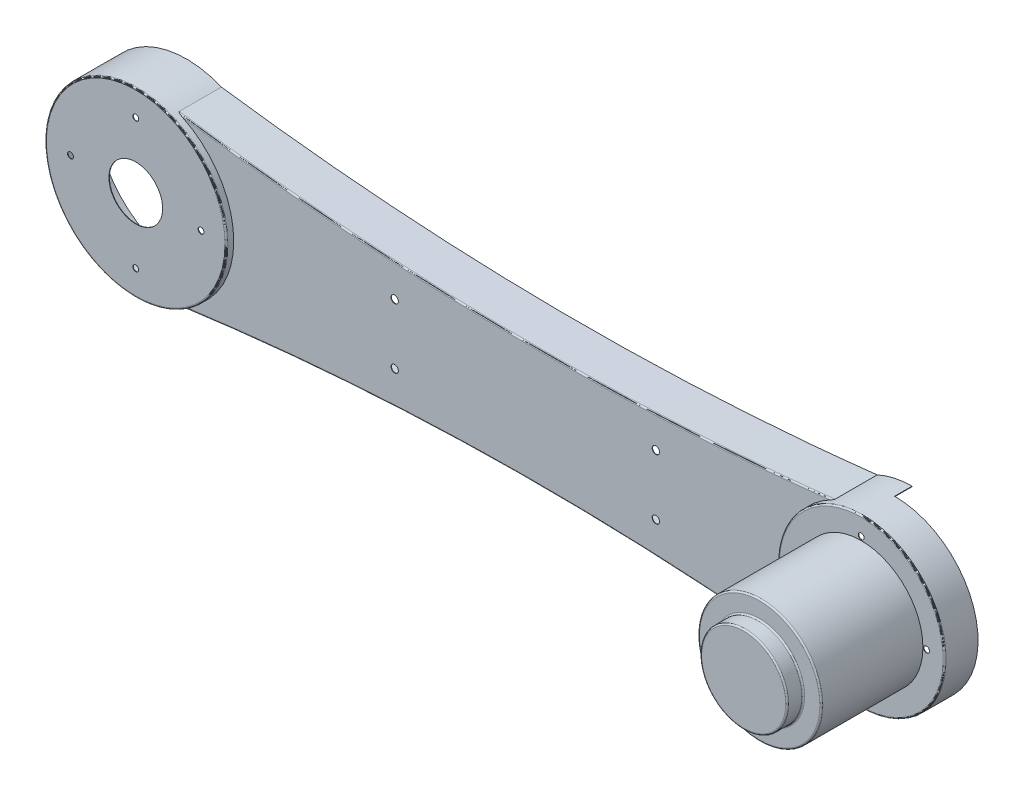
SolidWorks part; units mm, degrees
ref_plane "Front Plane" through (0, 0, 0) normal (0, 0, 1) x (1, 0, 0)
ref_plane "Top Plane" through (0, 0, 0) normal (0, 1, 0) x (1, 0, 0)
ref_plane "Right Plane" through (0, 0, 0) normal (1, 0, 0) x (0, 0, -1)
sketch "Sketch1" plane through (0, 0, 0) normal (0, 0, 1) x (1, 0, 0)
  line L0 (0, 0) -> (500, 0) construction
  line L1 (250, 0) -> (250, 152.9832) construction
  line L2 (24, 57.7083) -> (24, -57.7083) construction
  line L3 (476, 52.2518) -> (476, -52.2518) construction
  line L4 (0, 0) -> (0, 78.9019) construction
  circle A0 centre (0, 0) radius 62.5
  circle A1 centre (500, 0) radius 57.5
  spline S0 degree 2 poles (24, 57.7083) (249.6559, 26.362) (476, 52.2518) knots 0 0 0 1 1 1
  spline S1 degree 2 poles (24, -57.7083) (249.6559, -26.362) (476, -52.2518) knots 0 0 0 1 1 1
  dimension "D1" = 125
  dimension "D3" = 115
  dimension "D2" = 500
  dimension "D4" = 24
extrude "Boss-Extrude1" add sketch "Sketch1" along normal blind 35 contours A0 | A1 region at (0, 0, 0) region at (500, 0, 0)
extrude "Boss-Extrude2" add sketch "Sketch1<3>" along normal blind 30 contours A0 A1 region at (248.7459, 0, 0)
sketch "Sketch1<3>" plane through (0, 0, 0) normal (0, 0, 1) x (1, 0, 0) same geometry as "Sketch1"
sketch "Sketch8" plane through (0, 0, 35) normal (0, 0, 1) x (1, 0, 0)
  circle A0 centre (500, 0) radius 42.5
  dimension "D1" = 85
extrude "Boss-Extrude3" add sketch "Sketch8" along normal blind 70
sketch "Sketch9" plane through (0, 0, 105) normal (0, 0, 1) x (1, 0, 0)
  circle A0 centre (500, 0) radius 30
  dimension "D1" = 60
extrude "Boss-Extrude4" add sketch "Sketch9" along normal blind 11
shell "Shell1" thickness 0.3 removed face at (135.75, 0, 0)
sketch "Sketch2" plane through (0, 0, 34.7) normal (0, 0, -1) x (-1, 0, 0)
  circle A0 centre (0, 0) radius 57.5
  dimension "D1" = 115
sketch "Sketch3" plane through (0, 0, 34.7) normal (0, 0, -1) x (-1, 0, 0)
  circle A1 centre (0, 0) radius 62.5
  circle A2 centre (-500, 0) radius 57.5
  dimension "D1" = 125
  dimension "D2" = 115
fillet "Fillet1" radius 1 7 edges at (557.5, 0, 35) (62.5, 0, 35) (530, 0, 116) (542.5, 0, 105) (530, 0, 105)
hole_wizard "Ø4.0mm Dowel Hole1" positions "Sketch4" profile "Sketch5" hole size "Ø4.0" standard "ISO"
sketch "Sketch4" plane through (0, 0, 35) normal (0, 0, 1) x (1, 0, 0)
  line L0 (0, 0) -> (0, 45) construction
  circle A0 centre (0, 0) radius 45 construction
  circle A1 centre (500, 0) radius 45 construction
  point P2 (0, 45)
  point P16 (45, 0)
  point P17 (0, -45)
  point P18 (-45, 0)
  point P24 (500, 45)
  point P29 (545, 0)
  point P30 (500, -45)
  point P31 (455, 0)
  dimension "D1" = 90
  dimension "D3" = 90
  dimension "D2" = 4
  dimension "D4" = 4
sketch "Sketch5" plane through (455, 0, 35) normal (1, 0, 0) x (0, -1, 0)
  line L0 (0, 0) -> (0, 6)
  line L1 (0, 6) -> (2, 4.7983)
  line L2 (2, 4.7983) -> (2, 0.025)
  line L3 (2, 0.025) -> (2.025, 0)
  line L5 (2.025, 0) -> (0, 0)
  line L6 (-2, 0.025) -> (-2.025, 0) construction
  line L10 (0, 6) -> (-2, 4.7983) construction
  line L11 (0, -6.35) -> (0, 107.95) construction
  dimension "Hole Dia." = 4
  dimension "Hole Depth" = 6
  dimension "Near C'Sink Dia." = 4.05
  dimension "Near C'Sink Angle" = 90
  dimension "Drill Angle" = 118
sketch "Sketch6" plane through (0, 0, 0) normal (0, 0, -1) x (-1, 0, 0)
  line L1 (-500, 57.5) -> (-516.8399, -54.9788)
  line L2 (-606.5856, 15.1339) -> (-625.8242, -96.5521)
  arc A0 (-476, 52.2518) -> (-476, -52.2518) centre (-500, 0) ccw construction
  arc A1 (-500, 57.5) -> (-516.8399, -54.9788) centre (-500, 0) ccw
  arc A4 (-606.5856, 15.1339) -> (-625.8242, -96.5521) centre (-606.5856, -42.3661) ccw
extrude "Cut-Extrude1" cut sketch "Sketch6" against normal blind 12
sketch "Sketch10" plane through (0, 0, 35) normal (0, 0, 1) x (1, 0, 0)
  circle A0 centre (0, 0) radius 18.5
  dimension "D1" = 37
extrude "Cut-Extrude2" cut sketch "Sketch10" against normal blind 10
sketch "Sketch12" plane through (0, 0, 30) normal (0, 0, 1) x (1, 0, 0)
  circle A0 centre (173.4315, -20.7143) radius 2.525
  circle A1 centre (353.4315, -20.7143) radius 2.525
  circle A2 centre (353.4315, 20.7143) radius 2.525
  circle A3 centre (173.4315, 20.7143) radius 2.525
extrude "Cut-Extrude3" cut sketch "Sketch12" against normal blind 88.6
